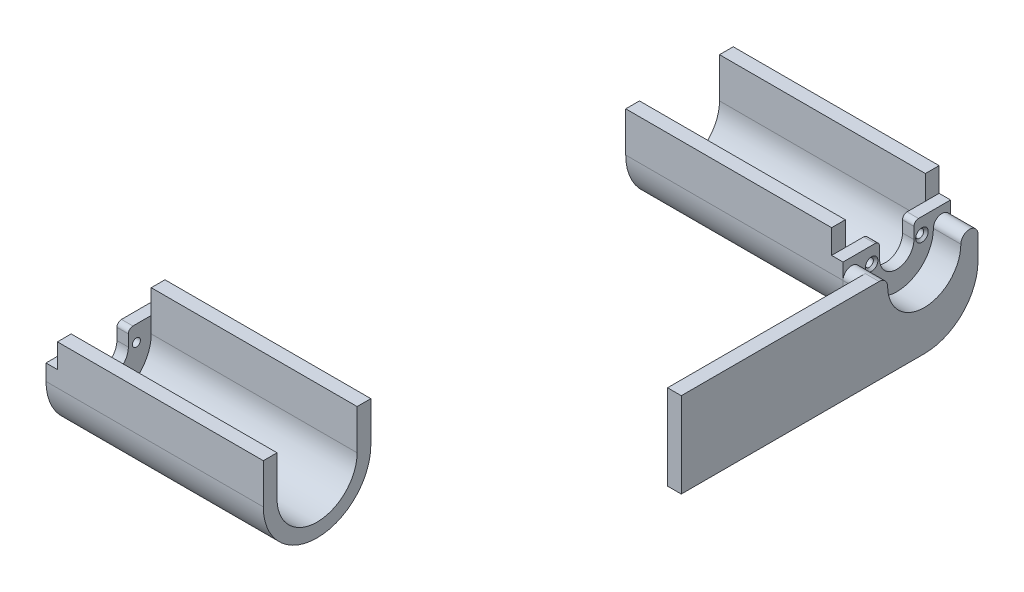
SolidWorks part; units mm, degrees
ref_plane "Front Plane" through (0, 0, 0) normal (0, 0, 1) x (1, 0, 0)
ref_plane "Top Plane" through (0, 0, 0) normal (0, 1, 0) x (1, 0, 0)
ref_plane "Right Plane" through (0, 0, 0) normal (1, 0, 0) x (0, 0, -1)
ref_axis "Center Axis" through (0, 23.7128, 0) along (0, -1, 0)
sketch "Sketch1" plane through (0, 0, 0) normal (1, 0, 0) x (0, 0, -1)
  line L0 (-159.8432, -20) -> (183.538, -20) construction
  line L1 (23.9696, -38.5304) -> (68.7681, 6.2681) construction
  line L2 (44.3566, -9.3934) -> (44.3566, -0.6434)
  line L3 (61.8566, -9.3934) -> (61.8566, -0.6434)
  line L4 (64.8566, -9.3934) -> (64.8566, -0.6434)
  line L5 (41.3566, -9.3934) -> (41.3566, -0.6434)
  line L6 (41.3566, -0.6434) -> (44.3566, -0.6434)
  line L7 (61.8566, -0.6434) -> (64.8566, -0.6434)
  arc A0 (44.3566, -9.3934) -> (61.8566, -9.3934) centre (53.1066, -9.3934) ccw
  arc A1 (41.3566, -9.3934) -> (64.8566, -9.3934) centre (53.1066, -9.3934) ccw
  point P1 (42.5, -20)
  dimension "D1" = 20
  dimension "D4" = 8.75
  dimension "D2" = 42.5
  dimension "D3" = 45
  dimension "D5" = 8.75
  dimension "D6" = 15
  dimension "D7" = 3
extrude "FrontMotorBracket" add sketch "Sketch1" along normal blind 45 from offset 13.5 offset against normal yes
sketch "Sketch8" plane through (0, 0, 0) normal (1, 0, 0) x (0, 0, -1)
  line L0 (-79.9426, -20) -> (109.5131, -20) construction
  line L1 (-68.835, 6.335) -> (-18.9148, -43.5852) construction
  line L2 (-61.8566, -9.3934) -> (-61.8566, -0.6434)
  line L3 (-41.3566, -0.6434) -> (-41.3566, -9.3934)
  line L4 (-44.3566, -0.6434) -> (-44.3566, -9.3934)
  line L5 (-64.8566, -9.3934) -> (-64.8566, -0.6434)
  line L6 (-64.8566, -0.6434) -> (-61.8566, -0.6434)
  line L7 (-44.3566, -0.6434) -> (-41.3566, -0.6434)
  arc A0 (-61.8566, -9.3934) -> (-44.3566, -9.3934) centre (-53.1066, -9.3934) ccw
  arc A1 (-64.8566, -9.3934) -> (-41.3566, -9.3934) centre (-53.1066, -9.3934) ccw
  point P5 (-42.5, -20)
  dimension "D5" = 8.75
  dimension "D1" = 20
  dimension "D2" = 42.5
  dimension "D3" = 45
  dimension "D4" = 15
  dimension "D6" = 8.75
  dimension "D7" = 3
extrude "RearMotorBracket" add sketch "Sketch8" against normal blind 45 from offset 13.5 separate body
sketch "Sketch5" plane through (31.5, 0, 0) normal (1, 0, 0) x (0, 0, -1)
  line L0 (49.3566, -6.8934) -> (49.3566, -9.3934)
  line L1 (41.3566, -9.3934) -> (41.3566, -5.8934)
  line L3 (41.3566, -5.8934) -> (48.3566, -5.8934)
  line L4 (41.3566, -0.6434) -> (41.3566, -9.3934) construction
  line L5 (56.8566, -6.8934) -> (56.8566, -9.3934)
  line L6 (57.8566, -5.8934) -> (64.8566, -5.8934)
  line L7 (64.8566, -9.3934) -> (64.8566, -0.6434) construction
  line L8 (64.8566, -5.8934) -> (64.8566, -9.3934)
  arc A0 (41.3566, -9.3934) -> (64.8566, -9.3934) centre (53.1066, -9.3934) ccw construction
  arc A1 (41.3566, -9.3934) -> (64.8566, -9.3934) centre (53.1066, -9.3934) ccw
  arc A3 (48.3566, -5.8934) -> (49.3566, -6.8934) centre (48.3566, -6.8934) cw
  arc A4 (49.3566, -9.3934) -> (56.8566, -9.3934) centre (53.1066, -9.3934) ccw
  arc A5 (49.3566, -9.3934) -> (56.8566, -9.3934) centre (53.1066, -9.3934) ccw
  arc A6 (57.8566, -5.8934) -> (56.8566, -6.8934) centre (57.8566, -6.8934) ccw
  dimension "D3" = 1
  dimension "D4" = 1
  dimension "D2" = 3.5
  dimension "D1" = 5
extrude "FrontMotorPlate" add sketch "Sketch5" along normal blind 2.5
sketch "Sketch9" plane through (-31.5, 0, 0) normal (-1, 0, 0) x (0, 0, 1)
  line L0 (41.3566, -9.3934) -> (41.3566, -5.8934)
  line L1 (41.3566, -9.3934) -> (41.3566, -0.6434) construction
  line L2 (41.3566, -5.8934) -> (48.3566, -5.8934)
  line L3 (49.3566, -6.8934) -> (49.3566, -9.3934)
  line L4 (56.8566, -9.3934) -> (56.8566, -6.8934)
  line L5 (57.8566, -5.8934) -> (64.8566, -5.8934)
  line L6 (64.8566, -0.6434) -> (64.8566, -9.3934) construction
  line L7 (64.8566, -5.8934) -> (64.8566, -9.3934)
  arc A0 (41.3566, -9.3934) -> (64.8566, -9.3934) centre (53.1066, -9.3934) ccw construction
  arc A1 (41.3566, -9.3934) -> (64.8566, -9.3934) centre (53.1066, -9.3934) ccw
  arc A4 (48.3566, -5.8934) -> (49.3566, -6.8934) centre (48.3566, -6.8934) cw
  arc A5 (49.3566, -9.3934) -> (56.8566, -9.3934) centre (53.1066, -9.3934) ccw
  arc A6 (49.3566, -9.3934) -> (56.8566, -9.3934) centre (53.1066, -9.3934) ccw
  arc A7 (56.8566, -6.8934) -> (57.8566, -5.8934) centre (57.8566, -6.8934) cw
  dimension "D3" = 1
  dimension "D4" = 1
  dimension "D2" = 3.5
  dimension "D1" = 5
extrude "RearMotorPlate" add sketch "Sketch9" along normal blind 2.5
sketch "Sketch6" plane through (34, 0, 0) normal (1, 0, 0) x (0, 0, -1)
  line L0 (35.2696, -9.3934) -> (72.8501, -9.3934) construction
  line L1 (53.1066, 12.6171) -> (53.1066, -36.011) construction
  arc A0 (49.3566, -9.3934) -> (56.8566, -9.3934) centre (53.1066, -9.3934) ccw construction
  arc A1 (49.3566, -9.3934) -> (56.8566, -9.3934) centre (53.1066, -9.3934) ccw construction
  circle A2 centre (47.6066, -9.3934) radius 0.875
  circle A3 centre (58.6066, -9.3934) radius 0.875
  dimension "D2" = 1.75
  dimension "D1" = 11
extrude "FrontMotorScrewHoles" cut sketch "Sketch6" against normal up to next (2.5 mm away)
sketch "Sketch10" plane through (-34, 0, 0) normal (-1, 0, 0) x (0, 0, 1)
  line L0 (33.7961, -9.3934) -> (79.1637, -9.3934) construction
  line L1 (53.1066, 11.6109) -> (53.1066, -30.6773) construction
  arc A0 (49.3566, -9.3934) -> (56.8566, -9.3934) centre (53.1066, -9.3934) ccw construction
  arc A1 (49.3566, -9.3934) -> (56.8566, -9.3934) centre (53.1066, -9.3934) ccw construction
  circle A2 centre (47.6066, -9.3934) radius 0.875
  circle A3 centre (58.6066, -9.3934) radius 0.875
  dimension "D1" = 1.75
  dimension "D2" = 11
extrude "RearMotorScrewHoles" cut sketch "Sketch10" against normal up to next (2.5 mm away)
chamfer "FrontMotorScrewChamfer" distance 0.5 angle 45 2 edges at (34, -9.3934, -59.4816) (34, -9.3934, -48.4816)
chamfer "RearMotorScrewChamfer" distance 0.5 angle 45 2 edges at (-34, -9.3934, 59.4816) (-34, -9.3934, 48.4816)
sketch "Sketch13" plane through (34, 0, 0) normal (1, 0, 0) x (0, 0, -1)
  line L0 (41.3566, -9.3934) -> (41.3566, -14.3934)
  line L1 (64.8566, -9.3934) -> (64.8566, -14.3934)
  arc A1 (41.3566, -14.3934) -> (64.8566, -14.3934) centre (53.1066, -14.3934) ccw
  arc A2 (41.3566, -9.3934) -> (45.1066, -9.3934) centre (43.2316, -9.3934) cw
  arc A4 (64.8566, -9.3934) -> (61.1066, -9.3934) centre (62.9816, -9.3934) ccw
  arc A5 (61.1066, -9.3934) -> (45.1066, -9.3934) centre (53.1066, -9.3934) cw
  dimension "D1" = 8
  dimension "D2" = 5
extrude "Boss-Extrude2" add sketch "Sketch13" along normal blind 3
sketch "Sketch14" plane through (37, 0, 0) normal (1, 0, 0) x (0, 0, -1)
  line L0 (64.8566, -14.3934) -> (64.8566, -9.3934) construction
  line L1 (43.2316, -7.5184) -> (0, -7.5184)
  line L2 (64.8566, -14.3934) -> (64.8566, -9.3934)
  line L3 (53.1066, -26.1434) -> (0, -26.1434)
  line L4 (0, -7.5184) -> (0, -19.0666)
  line L5 (0, -26.1434) -> (0, -19.0666)
  arc A0 (45.1066, -9.3934) -> (41.3566, -9.3934) centre (43.2316, -9.3934) ccw construction
  arc A1 (45.1066, -9.3934) -> (61.1066, -9.3934) centre (53.1066, -9.3934) ccw construction
  arc A2 (64.8566, -9.3934) -> (61.1066, -9.3934) centre (62.9816, -9.3934) ccw construction
  arc A3 (43.2316, -7.5184) -> (45.1066, -9.3934) centre (43.2316, -9.3934) cw
  arc A4 (45.1066, -9.3934) -> (61.1066, -9.3934) centre (53.1066, -9.3934) ccw
  arc A5 (64.8566, -9.3934) -> (61.1066, -9.3934) centre (62.9816, -9.3934) ccw
  arc A6 (64.8566, -14.3934) -> (53.1066, -26.1434) centre (53.1066, -14.3934) cw
  arc A7 (45.1066, -9.3934) -> (41.3566, -9.3934) centre (43.2316, -9.3934) ccw construction
  arc A8 (41.3566, -14.3934) -> (64.8566, -14.3934) centre (53.1066, -14.3934) ccw construction
extrude "Boss-Extrude3" add sketch "Sketch14" along normal blind 3
